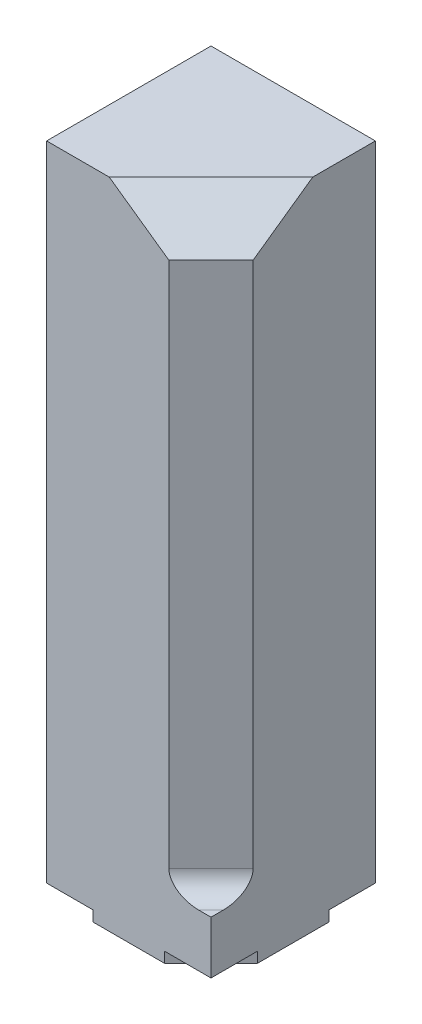
SolidWorks part; units mm, degrees
ref_plane "Front Plane" through (0, 0, 0) normal (0, 0, 1) x (1, 0, 0)
ref_plane "Top Plane" through (0, 0, 0) normal (0, 1, 0) x (1, 0, 0)
ref_plane "Right Plane" through (0, 0, 0) normal (1, 0, 0) x (0, 0, -1)
sketch "Sketch1" plane through (0, 0, 0) normal (0, 1, 0) x (1, 0, 0)
  line L1 (-1.95, 1.95) -> (1.95, 1.95)
  line L2 (-1.95, 1.95) -> (-1.95, -1.95)
  line L3 (-1.95, -1.95) -> (1.95, -1.95)
  line L4 (1.95, 1.95) -> (1.95, -1.95)
  line L5 (-1.95, 1.95) -> (1.95, -1.95) construction
  line L6 (-1.95, -1.95) -> (1.95, 1.95) construction
  point P0 (0, 0)
  dimension "D1" = 3.9
  dimension "D2" = 3.9
extrude "Boss-Extrude1" add sketch "Sketch1" along normal blind 15.5
ref_plane "Plane1" through (0, 0, 0) normal (0.7071, 0, 0.7071) x (0.7071, 0, -0.7071)
ref_point "Point1" parameters "D1"=1
ref_plane "Plane3" through (1.45, 0, 1.45) normal (0.7071, 0, 0.7071) x (0.7071, 0, -0.7071)
sketch "Sketch3" plane through (1.45, 0, 1.45) normal (0.7071, 0, 0.7071) x (0.7071, 0, -0.7071)
  line L0 (0, 15.5) -> (0, 0) construction
  line L1 (0, 15.5) -> (0, 0) construction
  line L2 (-2.7577, 0) -> (0, 0) construction
  line L3 (-1, 15.5) -> (1, 15.5)
  line L4 (-1, 15.5) -> (-1, 1.5)
  line L5 (-1, 1.5) -> (1, 1.5)
  line L6 (1, 15.5) -> (1, 1.5)
  line L7 (-1, 15.5) -> (1, 1.5) construction
  line L8 (-1, 1.5) -> (1, 15.5) construction
  point P2 (0, 8.5)
  point P7 (0, 15.5)
  dimension "D1" = 1.5
  dimension "D2" = 2
extrude "Cut-Extrude1" cut sketch "Sketch3" along normal through all
sketch "Sketch4" plane through (0, 0, 0) normal (0, -1, 0) x (1, 0, 0)
  line L0 (1.95, 1.95) -> (1.95, -1.95) construction
  line L1 (1.7, 1.7) -> (-1.7, 1.7)
  line L2 (1.7, 1.7) -> (1.7, -1.7)
  line L3 (1.7, -1.7) -> (-1.7, -1.7)
  line L4 (-1.7, 1.7) -> (-1.7, -1.7)
  line L5 (1.7, 1.7) -> (-1.7, -1.7) construction
  line L6 (1.7, -1.7) -> (-1.7, 1.7) construction
  line L7 (1.95, -1.95) -> (-1.95, -1.95) construction
  point P0 (0, 0)
  dimension "D1" = 0.25
  dimension "D2" = 0.25
extrude "Cut-Extrude2" cut sketch "Sketch4" against normal blind 0.25
sketch "Sketch5" plane through (0, 0, 0) normal (0, -1, 0) x (1, 0, 0)
  line L0 (1.95, 1.95) -> (0.85, 1.95)
  line L1 (-1.95, 1.95) -> (1.95, 1.95) construction
  line L2 (0.85, 1.95) -> (1.95, 0.85)
  line L3 (1.95, 1.95) -> (1.95, -1.95) construction
  line L4 (1.95, 0.85) -> (1.95, 1.95)
  line L5 (1.95, -1.95) -> (1.95, -0.85)
  line L6 (1.95, -0.85) -> (0.85, -1.95)
  line L7 (1.95, -1.95) -> (-1.95, -1.95) construction
  line L8 (0.85, -1.95) -> (1.95, -1.95)
  line L9 (-1.95, 1.95) -> (-0.85, 1.95)
  line L10 (-0.85, 1.95) -> (-1.95, 0.85)
  line L11 (-1.95, -1.95) -> (-1.95, 1.95) construction
  line L12 (-1.95, 0.85) -> (-1.95, 1.95)
  line L13 (-1.95, -1.95) -> (-0.85, -1.95)
  line L14 (-0.85, -1.95) -> (-1.95, -0.85)
  line L15 (-1.95, -0.85) -> (-1.95, -1.95)
  dimension "D1" = 1.1
extrude "Cut-Extrude3" cut sketch "Sketch5" against normal blind 0.25
ref_axis "Axis1" through (1.95, 0.25, 1.95) along (-0.7071, 0, -0.7071)
ref_axis "Axis2" through (-1.95, 0.25, 1.95) along (0.7071, 0, -0.7071)
ref_plane "Plane4" through (0, 0, 0) normal (0.7071, 0, 0.7071) x (0.7071, 0, -0.7071)
ref_plane "Plane5" through (0, 0, 0) normal (-0.7071, 0, 0.7071) x (0.7071, 0, 0.7071)
ref_axis "Axis3" through (0, -0.5125, 0) along (0, 1, 0)
chamfer "Chamfer1" distance 1 angle 45 1 edges at (1.45, 15.5, 1.45)
fillet "Fillet1" radius 0.5 1 edges at (1.45, 1.5, 1.45)
